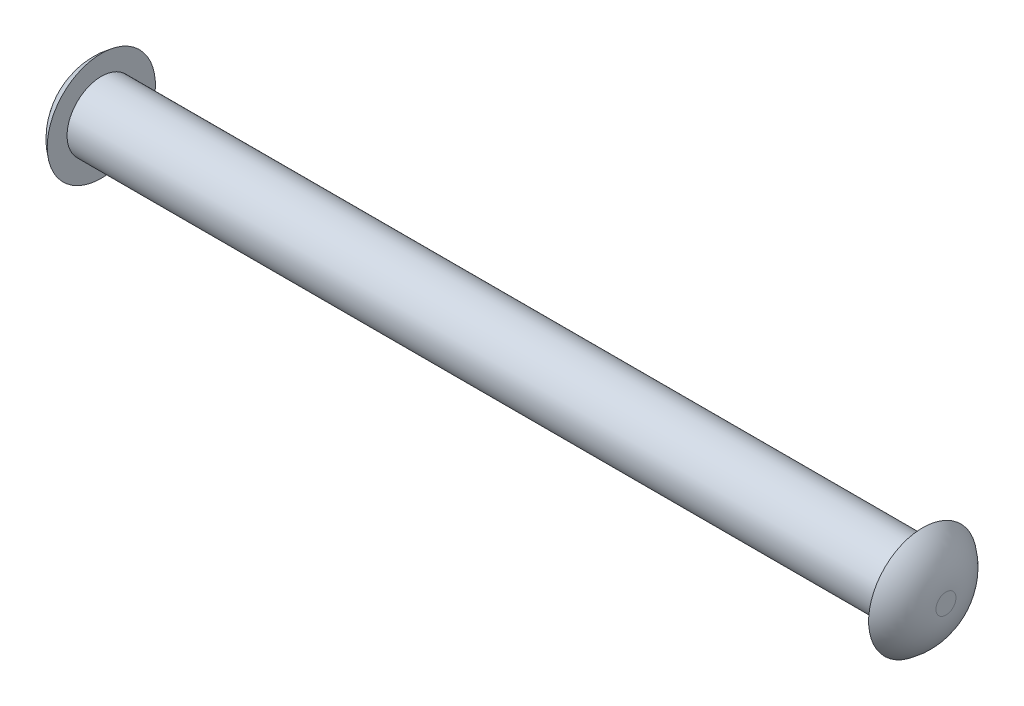
SolidWorks part; units mm, degrees
material "Нержавеющая сталь (ферритная)"
ref_plane "Спереди" through (0, 0, 0) normal (0, 0, 1) x (1, 0, 0)
ref_plane "Сверху" through (0, 0, 0) normal (0, 1, 0) x (1, 0, 0)
ref_plane "Справа" through (0, 0, 0) normal (1, 0, 0) x (0, 0, -1)
sketch "Эскиз1" plane through (0, 0, 0) normal (1, 0, 0) x (0, 0, -1)
  circle A0 centre (0, 0) radius 2.5
  dimension "D1" = 5
extrude "Бобышка-Вытянуть1" add sketch "Эскиз1" along normal blind 60
sketch "Эскиз2" plane through (0, 0, 0) normal (-1, 0, 0) x (0, 0, 1)
  circle A1 centre (0, 0) radius 3.95
  dimension "D1" = 7.9
extrude "Бобышка-Вытянуть2" add sketch "Эскиз2" along normal blind 1.7
sketch "Эскиз3" plane through (60, 0, 0) normal (1, 0, 0) x (0, 0, -1)
  circle A1 centre (0, 0) radius 3.95
  circle A2 centre (0, 0) radius 3.95
  dimension "D1" = 0
extrude "Бобышка-Вытянуть3" add sketch "Эскиз3" along normal blind 1.7
fillet "Скругление1" radius 3.9 2 edges at (-1.7, 0, 3.95) (61.7, 0, -3.95)
